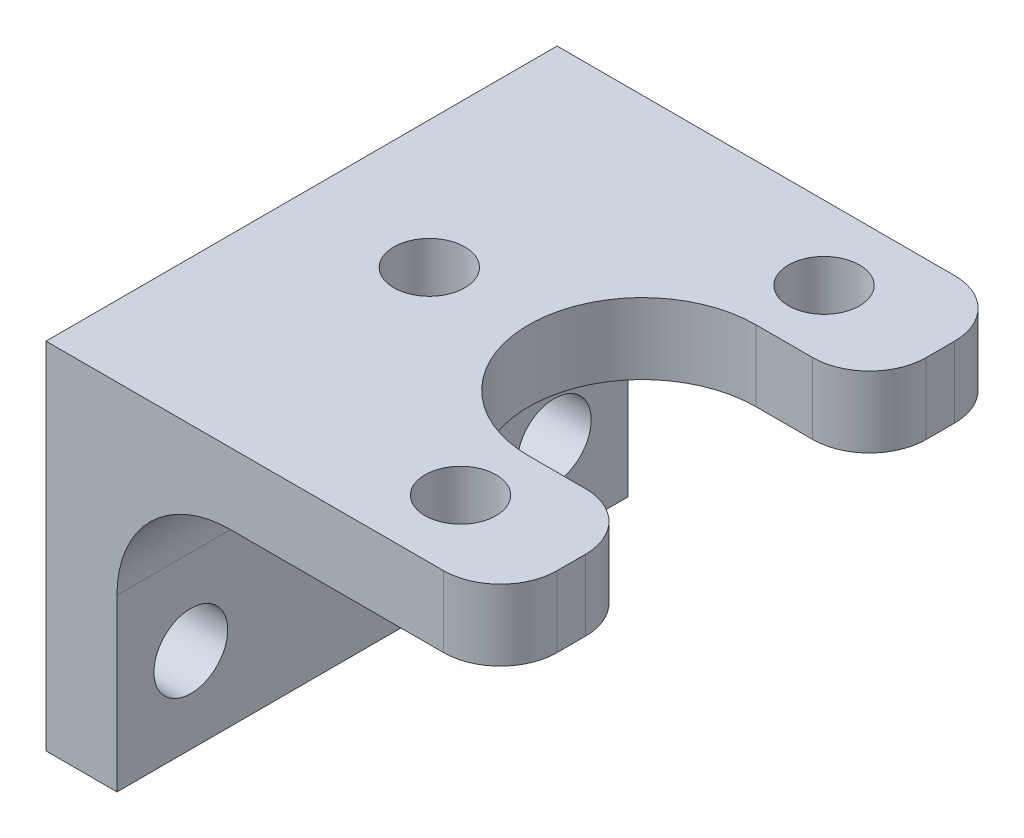
SolidWorks part; units mm, degrees
ref_plane "Front Plane" through (0, 0, 0) normal (0, 0, 1) x (1, 0, 0)
ref_plane "Top Plane" through (0, 0, 0) normal (0, 1, 0) x (1, 0, 0)
ref_plane "Right Plane" through (0, 0, 0) normal (1, 0, 0) x (0, 0, -1)
sketch "Sketch1" plane through (0, 0, 0) normal (0, 1, 0) x (1, 0, 0)
  line L1 (-10.16, -11.43) -> (10.16, -11.43)
  line L2 (-10.16, -11.43) -> (-10.16, 11.43)
  line L3 (-10.16, 11.43) -> (10.16, 11.43)
  line L4 (10.16, -11.43) -> (10.16, 11.43)
  line L5 (-10.16, -11.43) -> (10.16, 11.43) construction
  line L6 (-10.16, 11.43) -> (10.16, -11.43) construction
  point P0 (0, 0)
  dimension "D1" = 20.32
  dimension "D2" = 22.86
extrude "Boss-Extrude1" add sketch "Sketch1" along normal blind 3.175
fillet "Fillet1" radius 2.54 1 edges at (10.16, 1.5875, -11.43) type face fillet first side face at (10.16, 1.5875, 0) second side face at (0, 1.5875, -11.43)
fillet "Fillet2" radius 2.54 1 edges at (10.16, 1.5875, 11.43) type face fillet first side face at (10.16, 1.5875, 1.27) second side face at (0, 1.5875, 11.43)
sketch "Sketch2" plane through (0, 0, 0) normal (0, -1, 0) x (1, 0, 0)
  line L0 (-10.16, -11.43) -> (-10.16, 11.43) construction
  line L1 (7.62, -11.43) -> (-10.16, -11.43) construction
  line L2 (5.08, -5.08) -> (10.16, -5.08)
  line L3 (10.16, 8.89) -> (10.16, -8.89) construction
  line L4 (5.08, 5.08) -> (10.16, 5.08)
  line L5 (10.16, 5.08) -> (10.16, -5.08)
  arc A0 (5.08, 5.08) -> (5.08, -5.08) centre (5.08, 0) ccw
  dimension "D1" = 10.16
  dimension "D2" = 15.24
  dimension "D3" = 11.43
  dimension "D4" = 5.08
extrude "Cut-Extrude2" cut sketch "Sketch2" against normal through all
fillet "Fillet3" radius 2.54 1 edges at (10.16, 1.5875, 5.08) type face fillet first side face at (10.16, 1.5875, 6.985) second side face at (7.62, 1.5875, 5.08)
fillet "Fillet4" radius 2.54 1 edges at (10.16, 1.5875, -5.08) type face fillet first side face at (10.16, 1.5875, -6.985) second side face at (7.62, 1.5875, -5.08)
sketch "Sketch4" plane through (0, 0, 0) normal (0, -1, 0) x (1, 0, 0)
  line L0 (7.62, -11.43) -> (-10.16, -11.43) construction
  line L1 (-10.16, 11.43) -> (-6.985, 11.43)
  line L2 (-10.16, 11.43) -> (-10.16, -11.43)
  line L3 (-10.16, -11.43) -> (-6.985, -11.43)
  line L4 (-6.985, 11.43) -> (-6.985, -11.43)
  dimension "D1" = 3.175
extrude "Boss-Extrude2" add sketch "Sketch4" along normal blind 12.7
fillet "Fillet6" radius 5.08 1 edges type face fillet first side face at (5.3612, 0, -0.9525) second side face at (-6.985, -9.525, -2.8575)
sketch "Sketch3" plane through (0, 0, 0) normal (0, -1, 0) x (1, 0, 0)
  line L0 (7.62, -11.43) -> (-1.905, -11.43) construction
  line L1 (-1.905, 11.43) -> (7.62, 11.43) construction
  line L2 (-10.16, -11.43) -> (-10.16, 11.43) construction
  circle A0 centre (5.08, 8.128) radius 1.5875
  circle A1 centre (5.08, -8.128) radius 1.5875
  circle A2 centre (-4.445, 0) radius 1.5875
  dimension "D1" = 16.256
  dimension "D4" = 3.175
  dimension "D5" = 3.175
  dimension "D7" = 3.175
  dimension "D2" = 3.302
  dimension "D3" = 3.302
  dimension "D6" = 15.24
  dimension "D8" = 9.525
  dimension "D9" = 11.43
extrude "Cut-Extrude3" cut sketch "Sketch3" against normal mid plane 12.7
sketch "Sketch5" plane through (0, 0, 0) normal (0, -1, 0) x (1, 0, 0)
  line L0 (-10.16, 11.43) -> (-10.16, -11.43) construction
  line L1 (7.62, -11.43) -> (-1.905, -11.43) construction
  circle A0 centre (5.08, 0) radius 11.43
  dimension "D1" = 22.86
  dimension "D2" = 15.24
  dimension "D3" = 11.43
extrude "Cut-Extrude4" cut sketch "Sketch5" along normal blind 5.08
sketch "Sketch6" plane through (-6.985, 0, 0) normal (1, 0, 0) x (0, 0, -1)
  line L0 (11.43, -12.7) -> (11.43, -5.08) construction
  line L1 (-11.43, -12.7) -> (-11.43, -5.08) construction
  line L2 (11.43, -12.7) -> (-11.43, -12.7) construction
  circle A0 centre (-8.128, -8.89) radius 1.651
  circle A1 centre (8.128, -8.89) radius 1.651
  point P6 (-11.43, -8.89)
  dimension "D1" = 3.302
  dimension "D2" = 3.302
  dimension "D3" = 16.256
  dimension "D4" = 3.302
  dimension "D5" = 3.302
  dimension ".2" = 3.81
extrude "Cut-Extrude5" cut sketch "Sketch6" against normal through all
